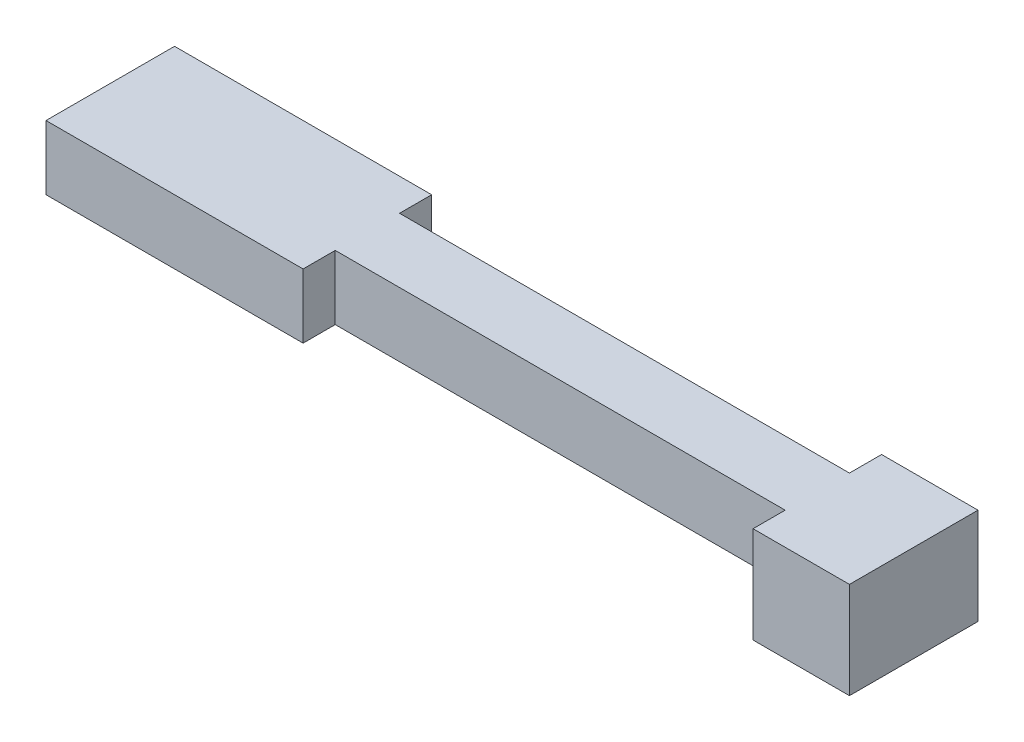
SolidWorks part; units mm, degrees
ref_plane "Front Plane" through (0, 0, 0) normal (0, 0, 1) x (1, 0, 0)
ref_plane "Top Plane" through (0, 0, 0) normal (0, 1, 0) x (1, 0, 0)
ref_plane "Right Plane" through (0, 0, 0) normal (1, 0, 0) x (0, 0, -1)
sketch "Sketch1" plane through (0, 0, 0) normal (0, 1, 0) x (1, 0, 0)
  line L1 (-20, -10) -> (20, -10)
  line L2 (-20, -10) -> (-20, 10)
  line L3 (-20, 10) -> (20, 10)
  line L4 (20, -10) -> (20, 10)
  line L5 (-20, -10) -> (20, 10) construction
  line L6 (-20, 10) -> (20, -10) construction
  line L7 (20, 5) -> (90, 5)
  line L8 (20, 5) -> (20, -5)
  line L9 (20, -5) -> (90, -5)
  line L10 (90, 5) -> (90, -5)
  line L11 (90, -10) -> (105, -10)
  line L12 (90, -10) -> (90, 10)
  line L13 (90, 10) -> (105, 10)
  line L14 (105, -10) -> (105, 10)
  point P0 (0, 0)
  point P10 (20, 0)
  point P11 (20, 0)
  point P16 (90, 0)
  point P17 (90, 0)
  dimension "D1" = 40
  dimension "D2" = 20
  dimension "D3" = 70
  dimension "D4" = 10
  dimension "D5" = 15
  dimension "D6" = 20
extrude "Boss-Extrude1" add sketch "Sketch1" along normal blind 10 contours L10 L7 L4 L9 | L1 L4 L3 L2 region at (0, 0, 0) region at (55, 0, 0)
extrude "Boss-Extrude2" add sketch "Sketch1<3>" against normal blind 15 from surface contours L11 L14 L13 L12 L10 region at (97.5, 0, 0) starting at face at (27.5, 10, 0)
sketch "Sketch1<3>" plane through (0, 0, 0) normal (0, 1, 0) x (1, 0, 0) same geometry as "Sketch1"
